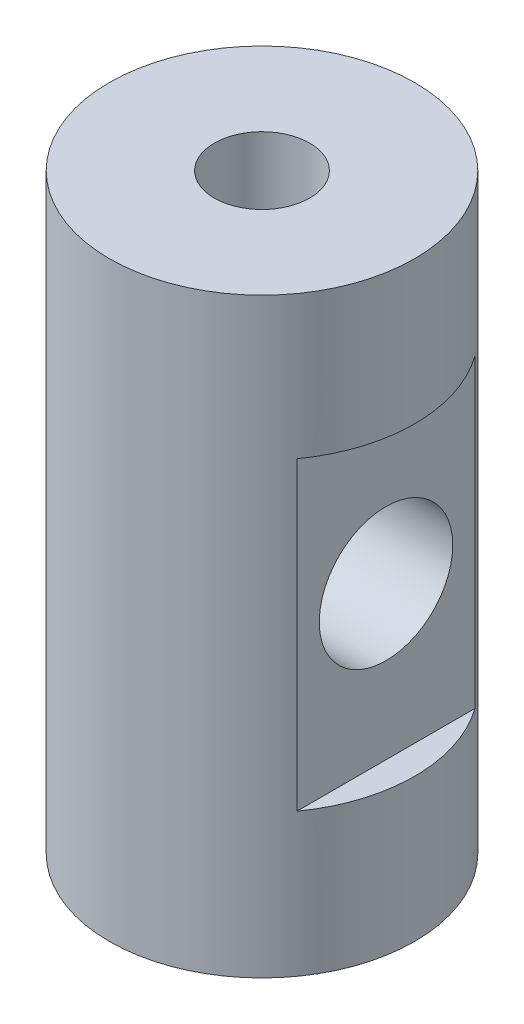
SolidWorks part; units mm, degrees
ref_plane "Front Plane" through (0, 0, 0) normal (0, 0, 1) x (1, 0, 0)
ref_plane "Top Plane" through (0, 0, 0) normal (0, 1, 0) x (1, 0, 0)
ref_plane "Right Plane" through (0, 0, 0) normal (1, 0, 0) x (0, 0, -1)
other "Configuration Table"
sketch "草图1" plane through (0, 0, 0) normal (0, 1, 0) x (1, 0, 0)
  circle A0 centre (0, 0) radius 8
  dimension "D1" = 16
extrude "凸台-拉伸1" add sketch "草图1" along normal blind 31
sketch "草图4" plane through (0, 31, 0) normal (0, 1, 0) x (1, 0, 0)
  point P0 (0, 0)
hole_wizard "M6x1.0 螺纹孔1" positions "草图4" profile "草图3" tap size "M6x1.0" standard "ANSI Metric"
sketch "草图3" plane through (0, 31, 0) normal (1, 0, 0) x (0, 0, 1)
  line L0 (0, 0) -> (0, 7.5022)
  line L1 (0, 7.5022) -> (2.5, 6)
  line L2 (2.5, 6) -> (2.5, 0)
  line L5 (2.5, 0) -> (0, 0)
  line L10 (0, 7.5022) -> (-2.5, 6) construction
  line L11 (0, -6.35) -> (0, 107.95) construction
  dimension "螺纹孔钻头直径" = 5
  dimension "螺纹孔钻头深度" = 6
  dimension "导头角度" = 118
cosmetic thread "孔螺纹线3" parameters "D1"=7, "D2"=6
sketch "草图7" plane through (0, 0, 0) normal (0, -1, 0) x (-1, 0, 0)
  point P0 (0, 0)
hole_wizard "M6x1.0 螺纹孔2" positions "草图7" profile "草图6" tap size "M6x1.0" standard "ANSI Metric"
sketch "草图6" plane through (0, 0, 0) normal (1, 0, 0) x (0, 0, -1)
  line L0 (0, 0) -> (0, 7.5022)
  line L1 (0, 7.5022) -> (2.5, 6)
  line L2 (2.5, 6) -> (2.5, 0)
  line L5 (2.5, 0) -> (0, 0)
  line L10 (0, 7.5022) -> (-2.5, 6) construction
  line L11 (0, -6.35) -> (0, 107.95) construction
  dimension "螺纹孔钻头直径" = 5
  dimension "螺纹孔钻头深度" = 6
  dimension "导头角度" = 118
cosmetic thread "孔螺纹线2" parameters "D1"=12, "D2"=6
sketch "草图10" plane through (0, 0, 0) normal (0, 0, 1) x (1, 0, 0)
  line L0 (0, 0) -> (0, 31) construction
  line L1 (-8, 0) -> (8, 0) construction
  line L2 (8, 31) -> (-8, 31) construction
  line L3 (0, 15.5) -> (6.5, 15.5) construction
  line L18 (6.5, 7.5) -> (6.5, 23.5)
  line L19 (6.5, 23.5) -> (8, 23.5)
  line L20 (8, 0) -> (8, 31) construction
  line L21 (8, 23.5) -> (8, 7.5)
  line L22 (8, 0) -> (8, 31) construction
  line L23 (8, 7.5) -> (6.5, 7.5)
  line L24 (-8, 23.5) -> (-8, 7.5)
  line L25 (-6.5, 23.5) -> (-8, 23.5)
  line L26 (-6.5, 7.5) -> (-6.5, 23.5)
  line L27 (-8, 7.5) -> (-6.5, 7.5)
  point P11 (6.5, 15.5)
extrude "切除-拉伸2" cut sketch "草图10" against normal blind 10 and the other way blind 10
sketch "草图11" plane through (6.5, 0, 0) normal (1, 0, 0) x (0, 0, -1)
  line L0 (0, 23.5) -> (0, 7.5) construction
  line L1 (-4.6637, 23.5) -> (4.6637, 23.5) construction
  line L2 (4.6637, 7.5) -> (-4.6637, 7.5) construction
sketch "草图16" plane through (6.5, 0, 0) normal (1, 0, 0) x (0, 0, -1)
  line L0 (0, 23.5) -> (0, 7.5) construction
  point P0 (0, 15.5)
hole_wizard "M8x1.0 螺纹孔1" positions "草图16" profile "草图15" tap size "M8x1.0" standard "ANSI Metric" end condition through all
sketch "草图15" plane through (6.5, 15.5, 0) normal (0, 1, 0) x (0, 0, -1)
  line L0 (0, 0) -> (0, 14.5)
  line L1 (0, 14.5) -> (3.5, 14.5)
  line L2 (3.5, 14.5) -> (3.5, 0)
  line L5 (3.5, 0) -> (0, 0)
  line L11 (0, -6.35) -> (0, 107.95) construction
  dimension "通孔螺纹孔钻头直径" = 7
  dimension "通孔螺纹孔钻头深度" = 14.5
cosmetic thread "孔螺纹线4" parameters "D2"=8
